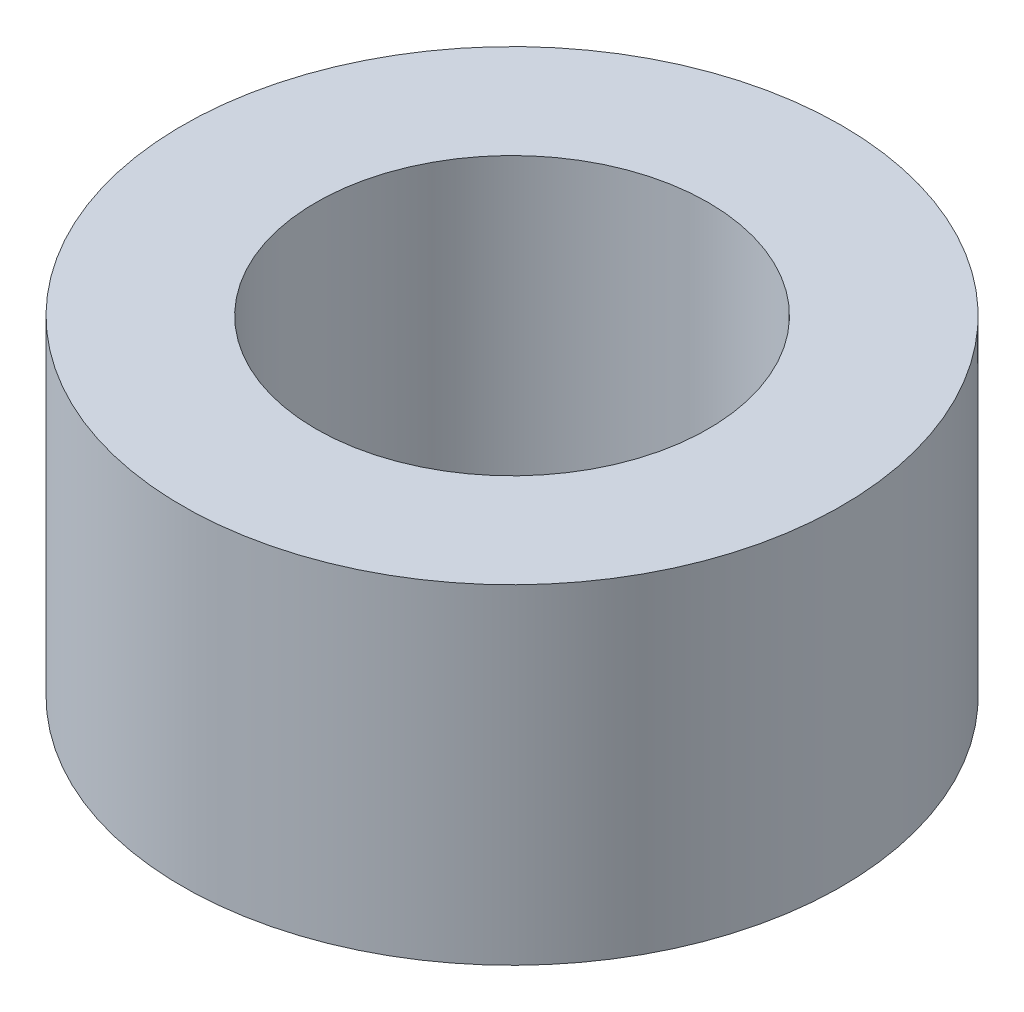
SolidWorks part; units mm, degrees
ref_plane "Alzado" through (0, 0, 0) normal (0, 0, 1) x (1, 0, 0)
ref_plane "Planta" through (0, 0, 0) normal (0, 1, 0) x (1, 0, 0)
ref_plane "Vista lateral" through (0, 0, 0) normal (1, 0, 0) x (0, 0, -1)
sketch "Croquis1" plane through (0, 0, 0) normal (0, 1, 0) x (1, 0, 0)
  circle A0 centre (0, 0) radius 12.5
  circle A1 centre (0, 0) radius 21
  dimension "D1" = 8.5
  dimension "D2" = 25
extrude "Saliente-Extruir1" add sketch "Croquis1" along normal blind 21
